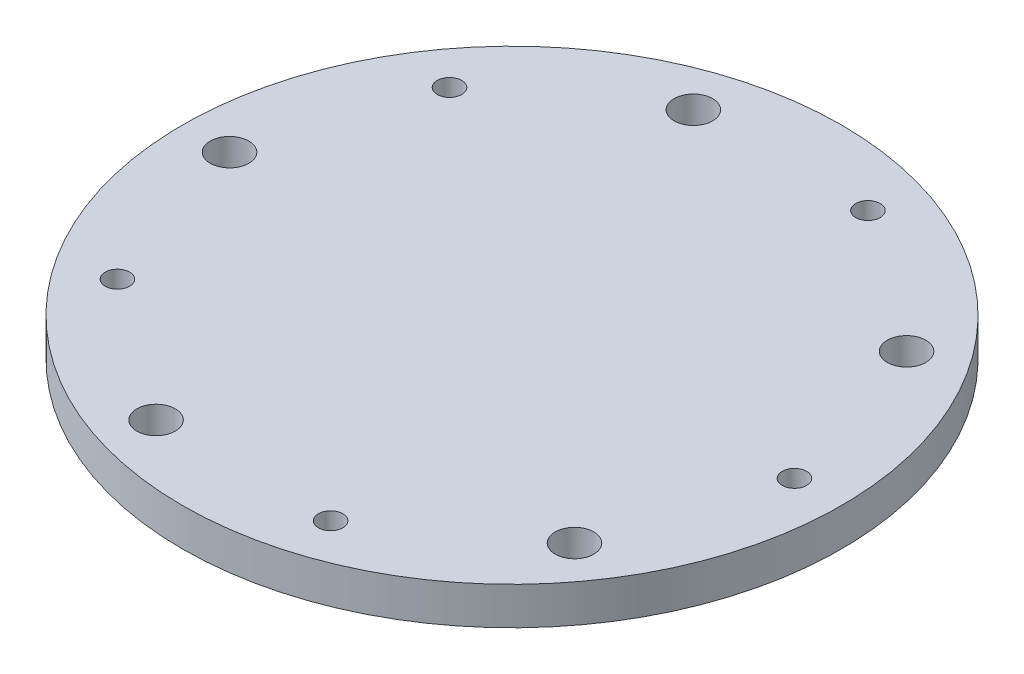
SolidWorks part; units mm, degrees
note: The reader was unsure of these and kept them because the rebuilt part matched: shared geometry of "Sketch19<3>".
other "Markup1"
sketch "Sketch22" plane through (67.4, 16.5, 67.4) normal (0.6133, 0.6241, 0.4841) x (0.6587, -0.0661, -0.7495)
sketch "Sketch37" plane through (67.4, 28, 67.4) normal (0.6133, 0.6241, 0.4841) x (0.6587, -0.0661, -0.7495)
other "Markup2"
sketch "Sketch23" plane through (67.4, 26.5, 67.4) normal (0.1362, 0.0894, 0.9866) x (0.9893, -0.0646, -0.1307)
sketch "Sketch38" plane through (67.4, 28, 67.4) normal (0.1362, 0.0894, 0.9866) x (0.9893, -0.0646, -0.1307)
other "Markup5"
sketch "Sketch28" plane through (-67.4, 30.5, 67.4) normal (-0.0176, 0.5562, 0.8308) x (0.9998, 0.0146, 0.0115)
sketch "Sketch39" plane through (-67.4, 28, 67.4) normal (-0.0176, 0.5562, 0.8308) x (0.9998, 0.0146, 0.0115)
material "1023 Carbon Steel Sheet (SS)"
ref_plane "Front Plane" through (0, 0, 0) normal (0, 0, 1) x (1, 0, 0)
ref_plane "Top Plane" through (0, 0, 0) normal (0, 1, 0) x (1, 0, 0)
ref_plane "Right Plane" through (0, 0, 0) normal (1, 0, 0) x (0, 0, -1)
sketch "Sketch1" plane through (0, 0, 0) normal (0, 0, 1) x (1, 0, 0)
  line L5 (-47.4, 0) -> (-47.4, -8)
  line L9 (-7, -8) -> (0, -8)
  line L10 (0, -8) -> (0, 0)
  line L12 (-7, -8) -> (-17.4, -8)
  line L24 (-17.4, -8) -> (-47.4, -8)
  line L25 (-47.4, 0) -> (0, 0)
  dimension "D2" = 8
  dimension "D3" = 47.4
  dimension "D8" = 0
  dimension "D10" = 7
revolve "Revolve1" add sketch "Sketch1" angle 360 about L10
sketch "Sketch4" plane through (0, 0, 0) normal (0, 0, 1) x (1, 0, 0)
  line L0 (0, 0) -> (0, 13.3666) construction
sketch "Sketch2" plane through (0, 0, 0) normal (0, 1, 0) x (1, 0, 0)
  circle A0 centre (-8, 0) radius 0.5
  dimension "D2" = 1
  dimension "D1" = 8
sketch "Sketch5" plane through (0, 0, 0) normal (1, 0, 0) x (0, 0, -1)
sketch "Sketch19" plane through (0, -8, 0) normal (0, -1, 0) x (1, 0, 0)
  line L0 (-47.4, 0) -> (-70, 0) construction
  line L1 (-56.6312, -41.145) -> (0, 0) construction
  line L4 (0, 0) -> (-66.574, -21.6312) construction
  line L5 (-51.8483, -13.5569) -> (-50.8815, -16.5324) construction
  line L9 (-69, 0) -> (-70, 0)
  line L11 (-53.7996, 39.0877) -> (-54.2257, 38.5013)
  circle A1 centre (0, 0) radius 47.4
  circle A2 centre (0, 0) radius 70 construction
  circle A3 centre (-60, 0) radius 4.1
  circle A4 centre (0, 0) radius 47.4 construction
  circle A5 centre (-48.541, -35.2671) radius 2.6
  circle A6 centre (0, 0) radius 53.5
  circle A8 centre (0, 0) radius 70
  spline S0 degree 3 poles (-50.8815, -16.5324) (-52.4491, -11.7078) (-59.9998, -9.5551) (-70, -7.7496) (-70, 0) knots 0 0 0 0 0.376166 1 1 1 1
  spline S1 degree 3 poles (-50.8815, -16.5324) (-49.3139, -21.357) (-54.1572, -27.5367) (-61.1863, -34.8754) (-56.6312, -41.145) knots 0 0 0 0 0.376166 1 1 1 1
  dimension "D2" = 8.2
  dimension "D5" = 5.2
  dimension "D7" = 107
  dimension "D3" = 60
  dimension "D4" = 36
  dimension "D6" = 60
  dimension "D8" = 18
  dimension "D1" = 22.6
extrude "Boss-Extrude2" add sketch "Sketch19" against normal blind 8
extrude "Bolt holes" cut sketch "Sketch19<3>" against normal up to surface (8 mm away) contours A3 | A5 up to face at (0, 0, -70)
sketch "Sketch19<3>" plane through (0, -8, 0) normal (0, -1, 0) x (1, 0, 0) same geometry as "Sketch19"
sketch "Sketch21" plane through (0, 0, 0) normal (0, 0, 1) x (1, 0, 0)
  line L0 (0, 0) -> (51.8972, 0) construction
  line L1 (0, 0) -> (0, -5.4672) construction
sketch "Sketch8" plane through (-29.8564, -8, 0) normal (0, -1, 0) x (-1, 0, 0)
  line L0 (-29.8564, 0) -> (-8.8564, 0) construction
  line L1 (-8.8564, 0) -> (-8.8564, 32.0516) construction
  circle A2 centre (-8.8564, 0) radius 1.75
  dimension "D1" = 3.5
  dimension "D2" = 21
ref_plane "Plane1" through (-21, 0, 0) normal (1, 0, 0) x (0, 0, -1)
ref_plane "Plane2" through (-1.7859, 3.0933, 0) normal (0.5, -0.866, 0) x (0, 0, -1)
sketch "Sketch41" plane through (-1.7859, 3.0933, 0) normal (0.5, -0.866, 0) x (0, 0, -1)
  circle A0 centre (0, -22.1865) radius 1.15
  dimension "D1" = 2.3
sketch "Sketch31" plane through (0, -8, 0) normal (0, -1, 0) x (1, 0, 0)
  circle A0 centre (0, 0) radius 27.4
  dimension "D1" = 54.8
sketch "Sketch32" plane through (0, 0, 0) normal (0, 1, 0) x (1, 0, 0)
  circle A0 centre (0, 0) radius 5.5 construction
  circle A1 centre (0, 0) radius 4.75
  dimension "M11_threads" = 11
  dimension "M11Tap" = 9.5
sketch "Sketch35" plane through (0, 0, 0) normal (0, 0, 1) x (1, 0, 0)
  line L0 (0, 0) -> (0, 22.3821) construction
pattern_circular "CirPattern10" count 5 over 360 about axis through (0, 0, 0) along (0, 1, 0) of "Bolt holes"
equation "\"Bolts\"= 10"
equation "\"D4@Sketch19\"=360/\"Bolts\""
equation "\"D7@Sketch19\"=102+2.5*2"
equation "\"D8@Sketch19\"=\"D4@Sketch19\"/2"
